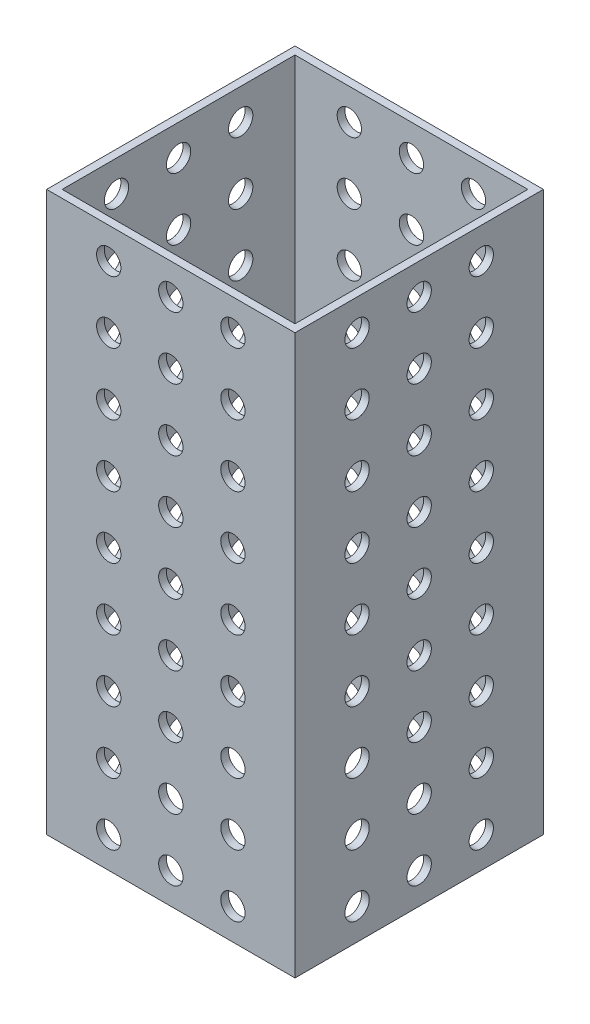
SolidWorks part; units mm, degrees
ref_plane "Front Plane" through (0, 0, 0) normal (0, 0, 1) x (1, 0, 0)
ref_plane "Top Plane" through (0, 0, 0) normal (0, 1, 0) x (1, 0, 0)
ref_plane "Right Plane" through (0, 0, 0) normal (1, 0, 0) x (0, 0, -1)
sketch "Sketch1" plane through (0, 0, 0) normal (0, 1, 0) x (1, 0, 0)
  line L1 (-25.4, 25.4) -> (25.4, 25.4)
  line L2 (-25.4, 25.4) -> (-25.4, -25.4)
  line L3 (-25.4, -25.4) -> (25.4, -25.4)
  line L4 (25.4, 25.4) -> (25.4, -25.4)
  line L5 (-25.4, 25.4) -> (25.4, -25.4) construction
  line L6 (-25.4, -25.4) -> (25.4, 25.4) construction
  line L7 (23.8125, 23.8125) -> (-23.8125, 23.8125)
  line L8 (23.8125, 23.8125) -> (23.8125, -23.8125)
  line L9 (23.8125, -23.8125) -> (-23.8125, -23.8125)
  line L10 (-23.8125, 23.8125) -> (-23.8125, -23.8125)
  line L11 (23.8125, 23.8125) -> (-23.8125, -23.8125) construction
  line L12 (23.8125, -23.8125) -> (-23.8125, 23.8125) construction
  point P0 (0, 0)
  point P6 (0, 0)
  dimension "D1" = 50.8
  dimension "D2" = 50.8
  dimension "D3" = 1.5875
  dimension "D4" = 1.5875
extrude "Boss-Extrude1" add sketch "Sketch1" along normal blind 685.8
sketch "Sketch2" plane through (0, 0, 25.4) normal (0, 0, 1) x (1, 0, 0)
  line L0 (0, 685.8) -> (0, 0) construction
  line L1 (-25.4, 685.8) -> (25.4, 685.8) construction
  line L2 (-25.4, 685.8) -> (-25.4, 0) construction
  line L3 (-6.35, -314.2) -> (-6.35, 49685.8) construction
  circle A0 centre (-12.7, 679.45) radius 2.4892
  circle A1 centre (-12.7, 666.75) radius 2.4892
  circle A2 centre (-12.7, 654.05) radius 2.4892
  circle A3 centre (-12.7, 641.35) radius 2.4892
  circle A4 centre (-12.7, 628.65) radius 2.4892
  circle A5 centre (-12.7, 615.95) radius 2.4892
  circle A6 centre (-12.7, 603.25) radius 2.4892
  circle A7 centre (-12.7, 590.55) radius 2.4892
  circle A8 centre (-12.7, 577.85) radius 2.4892
  circle A9 centre (-12.7, 565.15) radius 2.4892
  circle A10 centre (-12.7, 552.45) radius 2.4892
  circle A11 centre (-12.7, 539.75) radius 2.4892
  circle A12 centre (-12.7, 527.05) radius 2.4892
  circle A13 centre (-12.7, 514.35) radius 2.4892
  circle A14 centre (-12.7, 501.65) radius 2.4892
  circle A15 centre (-12.7, 488.95) radius 2.4892
  circle A16 centre (-12.7, 476.25) radius 2.4892
  circle A17 centre (-12.7, 463.55) radius 2.4892
  circle A18 centre (-12.7, 450.85) radius 2.4892
  circle A19 centre (-12.7, 438.15) radius 2.4892
  circle A20 centre (-12.7, 425.45) radius 2.4892
  circle A21 centre (-12.7, 412.75) radius 2.4892
  circle A22 centre (-12.7, 400.05) radius 2.4892
  circle A23 centre (-12.7, 387.35) radius 2.4892
  circle A24 centre (-12.7, 374.65) radius 2.4892
  circle A25 centre (-12.7, 361.95) radius 2.4892
  circle A26 centre (-12.7, 349.25) radius 2.4892
  circle A27 centre (-12.7, 336.55) radius 2.4892
  circle A28 centre (-12.7, 323.85) radius 2.4892
  circle A29 centre (-12.7, 311.15) radius 2.4892
  circle A30 centre (-12.7, 298.45) radius 2.4892
  circle A31 centre (-12.7, 285.75) radius 2.4892
  circle A32 centre (-12.7, 273.05) radius 2.4892
  circle A33 centre (-12.7, 260.35) radius 2.4892
  circle A34 centre (-12.7, 247.65) radius 2.4892
  circle A35 centre (-12.7, 234.95) radius 2.4892
  circle A36 centre (-12.7, 222.25) radius 2.4892
  circle A37 centre (-12.7, 209.55) radius 2.4892
  circle A38 centre (-12.7, 196.85) radius 2.4892
  circle A39 centre (-12.7, 184.15) radius 2.4892
  circle A40 centre (-12.7, 171.45) radius 2.4892
  circle A41 centre (-12.7, 158.75) radius 2.4892
  circle A42 centre (-12.7, 146.05) radius 2.4892
  circle A43 centre (-12.7, 133.35) radius 2.4892
  circle A44 centre (-12.7, 120.65) radius 2.4892
  circle A45 centre (-12.7, 107.95) radius 2.4892
  circle A46 centre (-12.7, 95.25) radius 2.4892
  circle A47 centre (-12.7, 82.55) radius 2.4892
  circle A48 centre (-12.7, 69.85) radius 2.4892
  circle A49 centre (-12.7, 57.15) radius 2.4892
  circle A50 centre (-12.7, 44.45) radius 2.4892
  circle A51 centre (-12.7, 31.75) radius 2.4892
  circle A52 centre (-12.7, 19.05) radius 2.4892
  circle A53 centre (-12.7, 6.35) radius 2.4892
  circle A54 centre (12.7, 6.35) radius 2.4892
  circle A55 centre (12.7, 19.05) radius 2.4892
  circle A56 centre (12.7, 31.75) radius 2.4892
  circle A57 centre (12.7, 44.45) radius 2.4892
  circle A58 centre (12.7, 57.15) radius 2.4892
  circle A59 centre (12.7, 69.85) radius 2.4892
  circle A60 centre (12.7, 82.55) radius 2.4892
  circle A61 centre (12.7, 95.25) radius 2.4892
  circle A62 centre (12.7, 107.95) radius 2.4892
  circle A63 centre (12.7, 120.65) radius 2.4892
  circle A64 centre (12.7, 133.35) radius 2.4892
  circle A65 centre (12.7, 146.05) radius 2.4892
  circle A66 centre (12.7, 158.75) radius 2.4892
  circle A67 centre (12.7, 171.45) radius 2.4892
  circle A68 centre (12.7, 184.15) radius 2.4892
  circle A69 centre (12.7, 196.85) radius 2.4892
  circle A70 centre (12.7, 209.55) radius 2.4892
  circle A71 centre (12.7, 222.25) radius 2.4892
  circle A72 centre (12.7, 234.95) radius 2.4892
  circle A73 centre (12.7, 247.65) radius 2.4892
  circle A74 centre (12.7, 260.35) radius 2.4892
  circle A75 centre (12.7, 273.05) radius 2.4892
  circle A76 centre (12.7, 285.75) radius 2.4892
  circle A77 centre (12.7, 298.45) radius 2.4892
  circle A78 centre (12.7, 311.15) radius 2.4892
  circle A79 centre (12.7, 323.85) radius 2.4892
  circle A80 centre (12.7, 336.55) radius 2.4892
  circle A81 centre (12.7, 374.65) radius 2.4892
  circle A82 centre (12.7, 361.95) radius 2.4892
  circle A83 centre (12.7, 349.25) radius 2.4892
  circle A84 centre (12.7, 387.35) radius 2.4892
  circle A85 centre (12.7, 400.05) radius 2.4892
  circle A86 centre (12.7, 412.75) radius 2.4892
  circle A87 centre (12.7, 425.45) radius 2.4892
  circle A88 centre (12.7, 438.15) radius 2.4892
  circle A89 centre (12.7, 450.85) radius 2.4892
  circle A90 centre (12.7, 463.55) radius 2.4892
  circle A91 centre (12.7, 476.25) radius 2.4892
  circle A92 centre (12.7, 488.95) radius 2.4892
  circle A93 centre (12.7, 501.65) radius 2.4892
  circle A94 centre (12.7, 514.35) radius 2.4892
  circle A95 centre (12.7, 527.05) radius 2.4892
  circle A96 centre (12.7, 539.75) radius 2.4892
  circle A97 centre (12.7, 552.45) radius 2.4892
  circle A98 centre (12.7, 565.15) radius 2.4892
  circle A99 centre (12.7, 577.85) radius 2.4892
  circle A100 centre (12.7, 590.55) radius 2.4892
  circle A101 centre (12.7, 603.25) radius 2.4892
  circle A102 centre (12.7, 615.95) radius 2.4892
  circle A103 centre (12.7, 628.65) radius 2.4892
  circle A104 centre (12.7, 641.35) radius 2.4892
  circle A105 centre (12.7, 654.05) radius 2.4892
  circle A106 centre (12.7, 666.75) radius 2.4892
  circle A107 centre (12.7, 679.45) radius 2.4892
  circle A108 centre (0, 6.35) radius 2.4892
  circle A109 centre (0, 19.05) radius 2.4892
  circle A110 centre (0, 31.75) radius 2.4892
  circle A111 centre (0, 44.45) radius 2.4892
  circle A112 centre (0, 57.15) radius 2.4892
  circle A113 centre (0, 69.85) radius 2.4892
  circle A114 centre (0, 82.55) radius 2.4892
  circle A115 centre (0, 95.25) radius 2.4892
  circle A116 centre (0, 107.95) radius 2.4892
  circle A117 centre (0, 120.65) radius 2.4892
  circle A118 centre (0, 133.35) radius 2.4892
  circle A119 centre (0, 146.05) radius 2.4892
  circle A120 centre (0, 158.75) radius 2.4892
  circle A121 centre (0, 171.45) radius 2.4892
  circle A122 centre (0, 184.15) radius 2.4892
  circle A123 centre (0, 196.85) radius 2.4892
  circle A124 centre (0, 209.55) radius 2.4892
  circle A125 centre (0, 222.25) radius 2.4892
  circle A126 centre (0, 234.95) radius 2.4892
  circle A127 centre (0, 247.65) radius 2.4892
  circle A128 centre (0, 260.35) radius 2.4892
  circle A129 centre (0, 273.05) radius 2.4892
  circle A130 centre (0, 285.75) radius 2.4892
  circle A131 centre (0, 298.45) radius 2.4892
  circle A132 centre (0, 311.15) radius 2.4892
  circle A133 centre (0, 323.85) radius 2.4892
  circle A134 centre (0, 336.55) radius 2.4892
  circle A135 centre (0, 349.25) radius 2.4892
  circle A136 centre (0, 361.95) radius 2.4892
  circle A137 centre (0, 374.65) radius 2.4892
  circle A138 centre (0, 387.35) radius 2.4892
  circle A139 centre (0, 400.05) radius 2.4892
  circle A140 centre (0, 412.75) radius 2.4892
  circle A141 centre (0, 425.45) radius 2.4892
  circle A142 centre (0, 438.15) radius 2.4892
  circle A143 centre (0, 450.85) radius 2.4892
  circle A144 centre (0, 463.55) radius 2.4892
  circle A145 centre (0, 476.25) radius 2.4892
  circle A146 centre (0, 488.95) radius 2.4892
  circle A147 centre (0, 501.65) radius 2.4892
  circle A148 centre (0, 514.35) radius 2.4892
  circle A149 centre (0, 527.05) radius 2.4892
  circle A150 centre (0, 539.75) radius 2.4892
  circle A151 centre (0, 552.45) radius 2.4892
  circle A152 centre (0, 565.15) radius 2.4892
  circle A153 centre (0, 577.85) radius 2.4892
  circle A154 centre (0, 590.55) radius 2.4892
  circle A155 centre (0, 603.25) radius 2.4892
  circle A156 centre (0, 615.95) radius 2.4892
  circle A157 centre (0, 628.65) radius 2.4892
  circle A158 centre (0, 641.35) radius 2.4892
  circle A159 centre (0, 654.05) radius 2.4892
  circle A160 centre (0, 666.75) radius 2.4892
  circle A161 centre (0, 679.45) radius 2.4892
  dimension "D1" = 4.9784
  dimension "D2" = 6.35
  dimension "D3" = 12.7
  dimension "D5" = 12.7
  dimension "D6" = 6.35
  dimension "D4" = 54
extrude "Cut-Extrude1" cut sketch "Sketch2" against normal through all
sketch "Sketch4" plane through (25.4, 0, 0) normal (1, 0, 0) x (0, 0, -1)
  line L0 (0, 685.8) -> (0, 0) construction
  line L1 (-25.4, 685.8) -> (25.4, 685.8) construction
  line L2 (-25.4, 685.8) -> (-25.4, 0) construction
  line L3 (-6.35, -314.2) -> (-6.35, 49685.8) construction
  circle A0 centre (-12.7, 679.45) radius 2.4892
  circle A1 centre (-12.7, 666.75) radius 2.4892
  circle A2 centre (-12.7, 654.05) radius 2.4892
  circle A3 centre (-12.7, 641.35) radius 2.4892
  circle A4 centre (-12.7, 628.65) radius 2.4892
  circle A5 centre (-12.7, 615.95) radius 2.4892
  circle A6 centre (-12.7, 603.25) radius 2.4892
  circle A7 centre (-12.7, 590.55) radius 2.4892
  circle A8 centre (-12.7, 577.85) radius 2.4892
  circle A9 centre (-12.7, 565.15) radius 2.4892
  circle A10 centre (-12.7, 552.45) radius 2.4892
  circle A11 centre (-12.7, 539.75) radius 2.4892
  circle A12 centre (-12.7, 527.05) radius 2.4892
  circle A13 centre (-12.7, 514.35) radius 2.4892
  circle A14 centre (-12.7, 501.65) radius 2.4892
  circle A15 centre (-12.7, 488.95) radius 2.4892
  circle A16 centre (-12.7, 476.25) radius 2.4892
  circle A17 centre (-12.7, 463.55) radius 2.4892
  circle A18 centre (-12.7, 450.85) radius 2.4892
  circle A19 centre (-12.7, 438.15) radius 2.4892
  circle A20 centre (-12.7, 425.45) radius 2.4892
  circle A21 centre (-12.7, 412.75) radius 2.4892
  circle A22 centre (-12.7, 400.05) radius 2.4892
  circle A23 centre (-12.7, 387.35) radius 2.4892
  circle A24 centre (-12.7, 374.65) radius 2.4892
  circle A25 centre (-12.7, 361.95) radius 2.4892
  circle A26 centre (-12.7, 349.25) radius 2.4892
  circle A27 centre (-12.7, 336.55) radius 2.4892
  circle A28 centre (-12.7, 323.85) radius 2.4892
  circle A29 centre (-12.7, 311.15) radius 2.4892
  circle A30 centre (-12.7, 298.45) radius 2.4892
  circle A31 centre (-12.7, 285.75) radius 2.4892
  circle A32 centre (-12.7, 273.05) radius 2.4892
  circle A33 centre (-12.7, 260.35) radius 2.4892
  circle A34 centre (-12.7, 247.65) radius 2.4892
  circle A35 centre (-12.7, 234.95) radius 2.4892
  circle A36 centre (-12.7, 222.25) radius 2.4892
  circle A37 centre (-12.7, 209.55) radius 2.4892
  circle A38 centre (-12.7, 196.85) radius 2.4892
  circle A39 centre (-12.7, 184.15) radius 2.4892
  circle A40 centre (-12.7, 171.45) radius 2.4892
  circle A41 centre (-12.7, 158.75) radius 2.4892
  circle A42 centre (-12.7, 146.05) radius 2.4892
  circle A43 centre (-12.7, 133.35) radius 2.4892
  circle A44 centre (-12.7, 120.65) radius 2.4892
  circle A45 centre (-12.7, 107.95) radius 2.4892
  circle A46 centre (-12.7, 95.25) radius 2.4892
  circle A47 centre (-12.7, 82.55) radius 2.4892
  circle A48 centre (-12.7, 69.85) radius 2.4892
  circle A49 centre (-12.7, 57.15) radius 2.4892
  circle A50 centre (-12.7, 44.45) radius 2.4892
  circle A51 centre (-12.7, 31.75) radius 2.4892
  circle A52 centre (-12.7, 19.05) radius 2.4892
  circle A53 centre (-12.7, 6.35) radius 2.4892
  circle A54 centre (12.7, 273.05) radius 2.4892
  circle A55 centre (12.7, 285.75) radius 2.4892
  circle A56 centre (12.7, 298.45) radius 2.4892
  circle A57 centre (12.7, 311.15) radius 2.4892
  circle A58 centre (12.7, 323.85) radius 2.4892
  circle A59 centre (12.7, 336.55) radius 2.4892
  circle A60 centre (12.7, 349.25) radius 2.4892
  circle A61 centre (12.7, 361.95) radius 2.4892
  circle A62 centre (12.7, 374.65) radius 2.4892
  circle A63 centre (12.7, 387.35) radius 2.4892
  circle A64 centre (12.7, 400.05) radius 2.4892
  circle A65 centre (12.7, 412.75) radius 2.4892
  circle A66 centre (12.7, 425.45) radius 2.4892
  circle A67 centre (12.7, 438.15) radius 2.4892
  circle A68 centre (12.7, 450.85) radius 2.4892
  circle A69 centre (12.7, 463.55) radius 2.4892
  circle A70 centre (12.7, 476.25) radius 2.4892
  circle A71 centre (12.7, 488.95) radius 2.4892
  circle A72 centre (12.7, 501.65) radius 2.4892
  circle A73 centre (12.7, 514.35) radius 2.4892
  circle A74 centre (12.7, 527.05) radius 2.4892
  circle A75 centre (12.7, 539.75) radius 2.4892
  circle A76 centre (12.7, 552.45) radius 2.4892
  circle A77 centre (12.7, 565.15) radius 2.4892
  circle A78 centre (12.7, 577.85) radius 2.4892
  circle A79 centre (12.7, 590.55) radius 2.4892
  circle A80 centre (12.7, 603.25) radius 2.4892
  circle A81 centre (12.7, 615.95) radius 2.4892
  circle A82 centre (12.7, 628.65) radius 2.4892
  circle A83 centre (12.7, 641.35) radius 2.4892
  circle A84 centre (12.7, 654.05) radius 2.4892
  circle A85 centre (12.7, 666.75) radius 2.4892
  circle A86 centre (12.7, 19.05) radius 2.4892
  circle A87 centre (12.7, 31.75) radius 2.4892
  circle A88 centre (12.7, 44.45) radius 2.4892
  circle A89 centre (12.7, 57.15) radius 2.4892
  circle A90 centre (12.7, 69.85) radius 2.4892
  circle A91 centre (12.7, 82.55) radius 2.4892
  circle A92 centre (12.7, 95.25) radius 2.4892
  circle A93 centre (12.7, 107.95) radius 2.4892
  circle A94 centre (12.7, 120.65) radius 2.4892
  circle A95 centre (12.7, 133.35) radius 2.4892
  circle A96 centre (12.7, 146.05) radius 2.4892
  circle A97 centre (12.7, 158.75) radius 2.4892
  circle A98 centre (12.7, 171.45) radius 2.4892
  circle A99 centre (12.7, 184.15) radius 2.4892
  circle A100 centre (12.7, 196.85) radius 2.4892
  circle A101 centre (12.7, 209.55) radius 2.4892
  circle A102 centre (12.7, 222.25) radius 2.4892
  circle A103 centre (12.7, 234.95) radius 2.4892
  circle A104 centre (12.7, 247.65) radius 2.4892
  circle A105 centre (12.7, 260.35) radius 2.4892
  circle A106 centre (12.7, 6.35) radius 2.4892
  circle A107 centre (12.7, 679.45) radius 2.4892
  circle A108 centre (0, 6.35) radius 2.4892
  circle A109 centre (0, 19.05) radius 2.4892
  circle A110 centre (0, 31.75) radius 2.4892
  circle A111 centre (0, 44.45) radius 2.4892
  circle A112 centre (0, 57.15) radius 2.4892
  circle A113 centre (0, 69.85) radius 2.4892
  circle A114 centre (0, 82.55) radius 2.4892
  circle A115 centre (0, 95.25) radius 2.4892
  circle A116 centre (0, 107.95) radius 2.4892
  circle A117 centre (0, 120.65) radius 2.4892
  circle A118 centre (0, 133.35) radius 2.4892
  circle A119 centre (0, 146.05) radius 2.4892
  circle A120 centre (0, 158.75) radius 2.4892
  circle A121 centre (0, 171.45) radius 2.4892
  circle A122 centre (0, 184.15) radius 2.4892
  circle A123 centre (0, 196.85) radius 2.4892
  circle A124 centre (0, 209.55) radius 2.4892
  circle A125 centre (0, 222.25) radius 2.4892
  circle A126 centre (0, 234.95) radius 2.4892
  circle A127 centre (0, 247.65) radius 2.4892
  circle A128 centre (0, 260.35) radius 2.4892
  circle A129 centre (0, 273.05) radius 2.4892
  circle A130 centre (0, 285.75) radius 2.4892
  circle A131 centre (0, 298.45) radius 2.4892
  circle A132 centre (0, 311.15) radius 2.4892
  circle A133 centre (0, 323.85) radius 2.4892
  circle A134 centre (0, 336.55) radius 2.4892
  circle A135 centre (0, 349.25) radius 2.4892
  circle A136 centre (0, 361.95) radius 2.4892
  circle A137 centre (0, 374.65) radius 2.4892
  circle A138 centre (0, 387.35) radius 2.4892
  circle A139 centre (0, 400.05) radius 2.4892
  circle A140 centre (0, 412.75) radius 2.4892
  circle A141 centre (0, 425.45) radius 2.4892
  circle A142 centre (0, 438.15) radius 2.4892
  circle A143 centre (0, 450.85) radius 2.4892
  circle A144 centre (0, 463.55) radius 2.4892
  circle A145 centre (0, 476.25) radius 2.4892
  circle A146 centre (0, 488.95) radius 2.4892
  circle A147 centre (0, 501.65) radius 2.4892
  circle A148 centre (0, 514.35) radius 2.4892
  circle A149 centre (0, 527.05) radius 2.4892
  circle A150 centre (0, 539.75) radius 2.4892
  circle A151 centre (0, 552.45) radius 2.4892
  circle A152 centre (0, 565.15) radius 2.4892
  circle A153 centre (0, 577.85) radius 2.4892
  circle A154 centre (0, 590.55) radius 2.4892
  circle A155 centre (0, 603.25) radius 2.4892
  circle A156 centre (0, 615.95) radius 2.4892
  circle A157 centre (0, 628.65) radius 2.4892
  circle A158 centre (0, 641.35) radius 2.4892
  circle A159 centre (0, 654.05) radius 2.4892
  circle A160 centre (0, 666.75) radius 2.4892
  circle A161 centre (0, 679.45) radius 2.4892
  dimension "D1" = 4.9784
  dimension "D2" = 12.7
  dimension "D3" = 6.35
  dimension "D5" = 12.7
  dimension "D6" = 6.35
  dimension "D4" = 54
extrude "Cut-Extrude2" cut sketch "Sketch4" against normal through all
sketch "Sketch5" plane through (25.4, 0, 0) normal (1, 0, 0) x (0, 0, -1)
  line L0 (25.4, 685.8) -> (25.4, 0) construction
  line L1 (-25.4, 685.8) -> (25.4, 685.8)
  line L2 (-25.4, 685.8) -> (-25.4, 114.3)
  line L3 (-25.4, 114.3) -> (25.4, 114.3)
  line L4 (25.4, 685.8) -> (25.4, 114.3)
  dimension "D1" = 571.5
extrude "Cut-Extrude3" cut sketch "Sketch5" against normal through all
